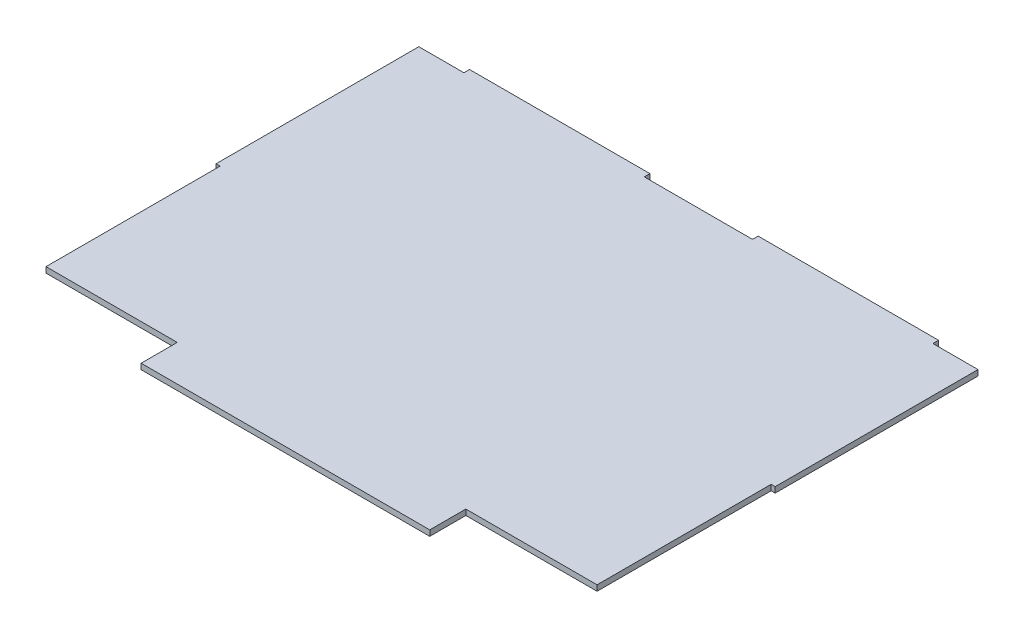
SolidWorks part; units mm, degrees
material "6061-T6 (SS)"
ref_plane "X-Y Datum" through (0, 0, 0) normal (0, 0, 1) x (1, 0, 0)
ref_plane "X-Z Datum" through (0, 0, 0) normal (0, 1, 0) x (1, 0, 0)
ref_plane "Y-Z Datum" through (0, 0, 0) normal (1, 0, 0) x (0, 0, -1)
sketch "Sketch1" plane through (0, 0, 0) normal (0, 0, 1) x (1, 0, 0)
  line L1 (-157.4823, -1.5875) -> (157.4823, -1.5875)
  line L2 (-157.4823, -1.5875) -> (-157.4823, 1.5875)
  line L3 (-157.4823, 1.5875) -> (157.4823, 1.5875)
  line L4 (157.4823, -1.5875) -> (157.4823, 1.5875)
  line L5 (-157.4823, -1.5875) -> (157.4823, 1.5875) construction
  line L6 (-157.4823, 1.5875) -> (157.4823, -1.5875) construction
  point P0 (0, 0)
  dimension "D1" = 314.9646
  dimension "D2" = 3.175
extrude "Boss-Extrude1" add sketch "Sketch1" along normal blind 235.775
sketch "Sketch3" plane through (0, 0, 0) normal (0, 0, -1) x (-1, 0, 0)
  line L0 (-157.4823, 0) -> (-81.2823, 0) construction
  line L1 (-157.4823, -1.5875) -> (-157.4823, 1.5875) construction
  line L2 (-157.4823, 1.5875) -> (157.4823, 1.5875) construction
  line L3 (-132.0823, -1.5875) -> (-30.4823, -1.5875)
  line L4 (-132.0823, -1.5875) -> (-132.0823, 1.5875)
  line L5 (-132.0823, 1.5875) -> (-30.4823, 1.5875)
  line L6 (-30.4823, -1.5875) -> (-30.4823, 1.5875)
  line L7 (-132.0823, -1.5875) -> (-30.4823, 1.5875) construction
  line L8 (-132.0823, 1.5875) -> (-30.4823, -1.5875) construction
  line L14 (-157.4823, 1.5875) -> (-132.0823, 1.5875)
  line L15 (-157.4823, 1.5875) -> (-157.4823, -1.5875)
  line L16 (-157.4823, -1.5875) -> (-132.0823, -1.5875)
  line L17 (-132.0823, 1.5875) -> (-132.0823, -1.5875)
  line L19 (-30.4823, 1.5875) -> (-30.4823, -1.5875)
  line L20 (0, 43.0151) -> (0, -43.0151) construction
  line L21 (30.4823, -1.5875) -> (30.4823, 1.5875)
  line L22 (132.0823, -1.5875) -> (132.0823, 1.5875)
  line L23 (132.0823, 1.5875) -> (30.4823, 1.5875)
  line L24 (132.0823, -1.5875) -> (30.4823, 1.5875) construction
  line L25 (132.0823, -1.5875) -> (30.4823, -1.5875)
  line L26 (132.0823, 1.5875) -> (30.4823, -1.5875) construction
  line M2 (-157.4823, 1.5875) -> (-157.4823, -1.5875)
  line M3 (-157.4823, -1.5875) -> (157.4823, -1.5875)
  line M4 (157.4823, -1.5875) -> (157.4823, 1.5875)
  line M5 (157.4823, 1.5875) -> (-157.4823, 1.5875)
  dimension "D1" = 76.2
  dimension "D2" = 101.6
extrude "Cut-Extrude1" cut sketch "Sketch3" against normal blind 3.175 contours L4 M3 M5 M2 | L6 M3 M5 | M3 M4 M5 region at (144.7823, 0, 0) region at (0, 0, 0) region at (-144.7823, 0, 0)
sketch "Sketch5" plane through (0, 1.5875, 0) normal (0, 1, 0) x (1, 0, 0)
  line L1 (-157.4823, -235.775) -> (-155.1963, -235.775)
  line L3 (-157.4823, -235.775) -> (-157.4823, -117.411)
  line L5 (-157.4823, -117.411) -> (-155.1963, -117.411)
  line L6 (-155.1963, -235.775) -> (-155.1963, -117.411)
  line M11 (-157.4823, -3.175) -> (-157.4823, -235.775)
  line M12 (-157.4823, -235.775) -> (157.4823, -235.775)
  dimension "D1" = 118.364
  dimension "D2" = 2.286
extrude "Cut-Extrude2" cut sketch "Sketch5" against normal blind 3.175 and the other way through all contours M12 M11 region at (-156.3393, 1.5875, 176.593)
mirror "Mirror1" about plane through (0, 0, 0) normal (1, 0, 0) of "Cut-Extrude2"
sketch "Sketch6" plane through (0, 1.5875, 0) normal (0, 1, 0) x (1, 0, 0)
  line L6 (-157.4823, -215.455) -> (-81.2823, -215.455)
  line L7 (-157.4823, -215.455) -> (-157.4823, -235.775)
  line L8 (-157.4823, -235.775) -> (-81.2823, -235.775)
  line L9 (-81.2823, -215.455) -> (-81.2823, -235.775)
  line L10 (155.1963, -235.775) -> (-155.1963, -235.775) construction
  line L11 (-157.4823, -117.411) -> (-157.4823, -3.175) construction
  line L13 (155.1963, -235.775) -> (-81.2823, -235.775)
  line L14 (155.1963, -235.775) -> (155.1963, -215.455)
  line L15 (155.1963, -215.455) -> (-81.2823, -215.455)
  line L16 (-81.2823, -235.775) -> (-81.2823, -215.455)
  line M18 (-155.1963, -117.411) -> (-155.1963, -235.775)
  line M19 (-155.1963, -235.775) -> (155.1963, -235.775)
  dimension "D1" = 76.2
  dimension "D2" = 20.32
extrude "Cut-Extrude4" cut sketch "Sketch6" against normal through all contours L9 L6 M18 M19 region at (-118.2393, 1.5875, 225.615)
sketch "Sketch7" [suppressed] plane through (0, 1.5875, 0) normal (0, 1, 0) x (1, 0, 0)
  line L1 (-81.2823, -215.455) -> (155.1963, -215.455)
  line L2 (-81.2823, -215.455) -> (-81.2823, -235.775)
  line L3 (-81.2823, -235.775) -> (155.1963, -235.775)
  line L4 (155.1963, -215.455) -> (155.1963, -235.775)
extrude "Cut-Extrude5" [suppressed] cut sketch "Sketch7" against normal through all
sketch "Sketch8" plane through (0, 1.5875, 0) normal (0, 1, 0) x (1, 0, 0)
  line L0 (155.1963, -235.775) -> (-81.2823, -235.775) construction
  line L1 (157.4823, -215.455) -> (81.2823, -215.455)
  line L2 (157.4823, -215.455) -> (157.4823, -235.775)
  line L3 (157.4823, -235.775) -> (81.2823, -235.775)
  line L4 (81.2823, -215.455) -> (81.2823, -235.775)
  line L5 (157.4823, -117.411) -> (157.4823, -3.175) construction
  dimension "D1" = 20.32
  dimension "D2" = 76.2
extrude "Cut-Extrude6" cut sketch "Sketch8" against normal through all
sketch "Sketch9" [suppressed] plane through (0, 0, 215.455) normal (0, 0, 1) x (1, 0, 0)
  line L4 (155.1963, 1.5875) -> (-155.1963, 1.5875)
  line L5 (-155.1963, 1.5875) -> (-155.1963, -1.5875)
  line L6 (-155.1963, -1.5875) -> (155.1963, -1.5875)
  line L7 (155.1963, -1.5875) -> (155.1963, 1.5875)
  line L8 (155.1963, 1.5875) -> (-155.1963, 1.5875)
  line L9 (-155.1963, 1.5875) -> (-155.1963, -1.5875)
  line L10 (-155.1963, -1.5875) -> (155.1963, -1.5875)
  line L11 (155.1963, -1.5875) -> (155.1963, 1.5875)
  dimension "D1" = 0
extrude "Cut-Extrude7" [suppressed] cut sketch "Sketch9" against normal blind 11.68
